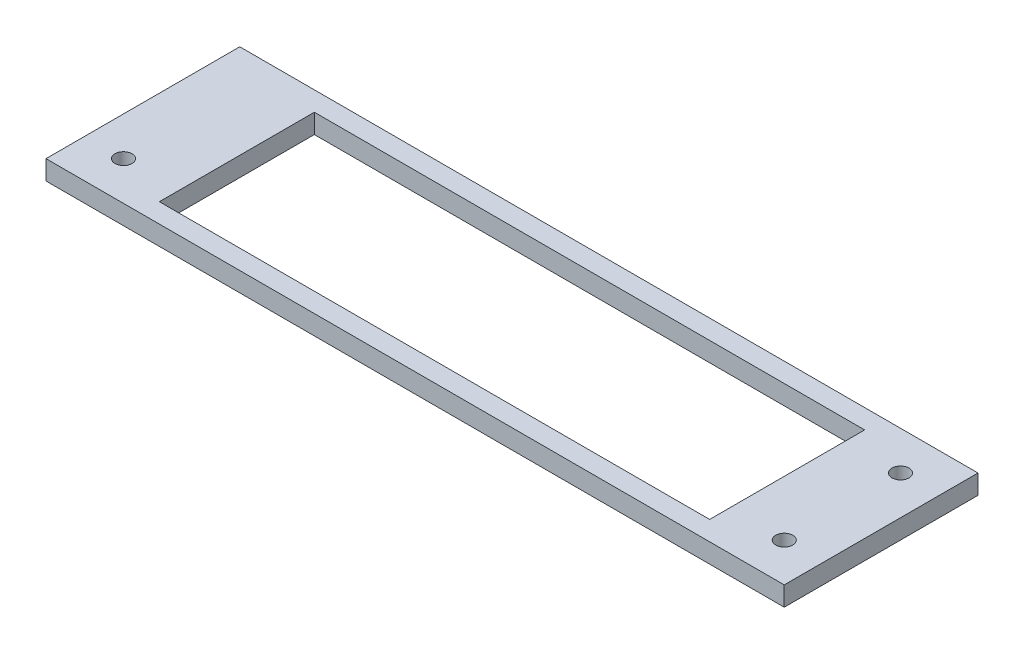
SolidWorks part; units mm, degrees
ref_plane "Front Plane" through (0, 0, 0) normal (0, 0, 1) x (1, 0, 0)
ref_plane "Top Plane" through (0, 0, 0) normal (0, 1, 0) x (1, 0, 0)
ref_plane "Right Plane" through (0, 0, 0) normal (1, 0, 0) x (0, 0, -1)
sketch "Sketch1" plane through (0, 0, 0) normal (0, 1, 0) x (1, 0, 0)
  line L1 (-95.25, 25) -> (95.25, 25)
  line L2 (-95.25, 25) -> (-95.25, -25)
  line L3 (-95.25, -25) -> (95.25, -25)
  line L4 (95.25, 25) -> (95.25, -25)
  line L5 (-95.25, 25) -> (95.25, -25) construction
  line L6 (-95.25, -25) -> (95.25, 25) construction
  point P0 (0, 0)
  dimension "D1" = 50
  dimension "D2" = 190.5
extrude "Boss-Extrude1" add sketch "Sketch1" along normal blind 5
sketch "Sketch2" plane through (0, 5, 0) normal (0, 1, 0) x (1, 0, 0)
  line L0 (-95.25, 25) -> (-95.25, -25) construction
  line L1 (-95.25, -25) -> (95.25, -25) construction
  line L2 (95.25, -25) -> (95.25, 25) construction
  line L3 (95.25, 25) -> (-95.25, 25) construction
  circle A0 centre (-85.25, -15) radius 2.2
  circle A1 centre (85.25, -15) radius 2.2
  circle A2 centre (85.25, 15) radius 2.2
  point P14 (0, 0)
  point P15 (0, 0)
  dimension "D1" = 4.4
  dimension "D2" = 10
  dimension "D3" = 10
  dimension "D4" = 10
  dimension "D5" = 10
extrude "Cut-Extrude1" cut sketch "Sketch2" against normal through all
sketch "Sketch4" plane through (0, 5, 0) normal (0, 1, 0) x (1, 0, 0)
  line L0 (95.25, 25) -> (-95.25, 25) construction
  line L1 (-71, 20) -> (71, 20)
  line L2 (-71, 20) -> (-71, -20)
  line L3 (-71, -20) -> (71, -20)
  line L4 (71, 20) -> (71, -20)
  line L5 (-71, 20) -> (71, -20) construction
  line L6 (-71, -20) -> (71, 20) construction
  point P0 (0, 0)
  point P7 (0, 0)
  point P8 (0, 25)
  dimension "D1" = 142
  dimension "D2" = 5
  dimension "D3" = 40
extrude "Cut-Extrude2" cut sketch "Sketch4" against normal up to surface (5 mm away) up to face at (-85.25, 0, 17.2)
